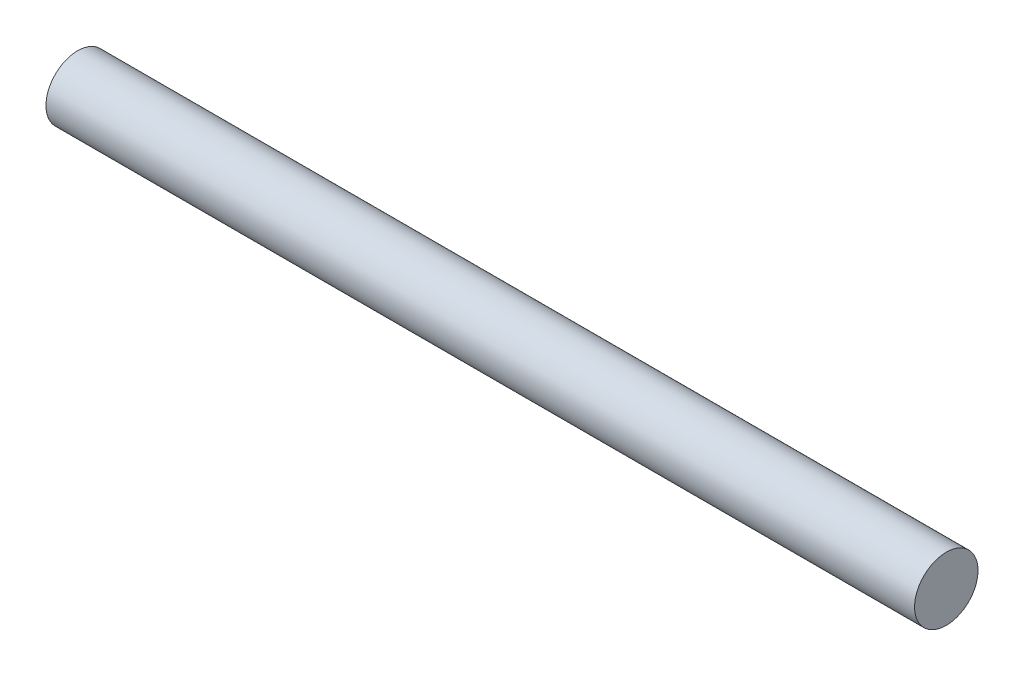
SolidWorks part; units mm, degrees
ref_plane "前视基准面" through (0, 0, 0) normal (0, 0, 1) x (1, 0, 0)
ref_plane "上视基准面" through (0, 0, 0) normal (0, 1, 0) x (1, 0, 0)
ref_plane "右视基准面" through (0, 0, 0) normal (1, 0, 0) x (0, 0, -1)
sketch "草图1" plane through (0, 0, 0) normal (1, 0, 0) x (0, 0, -1)
  circle A0 centre (0, 0) radius 4
  dimension "D1" = 8
extrude "凸台-拉伸1" add sketch "草图1" along normal blind 150
sketch "草图4" plane through (0, 0, 0) normal (-1, 0, 0) x (0, 0, 1)
  circle A1 centre (0, 0) radius 4
  circle A2 centre (0, 0) radius 4
  dimension "D1" = 0
extrude "切除-拉伸1" cut sketch "草图4" against normal up to surface (40.5 mm away)
